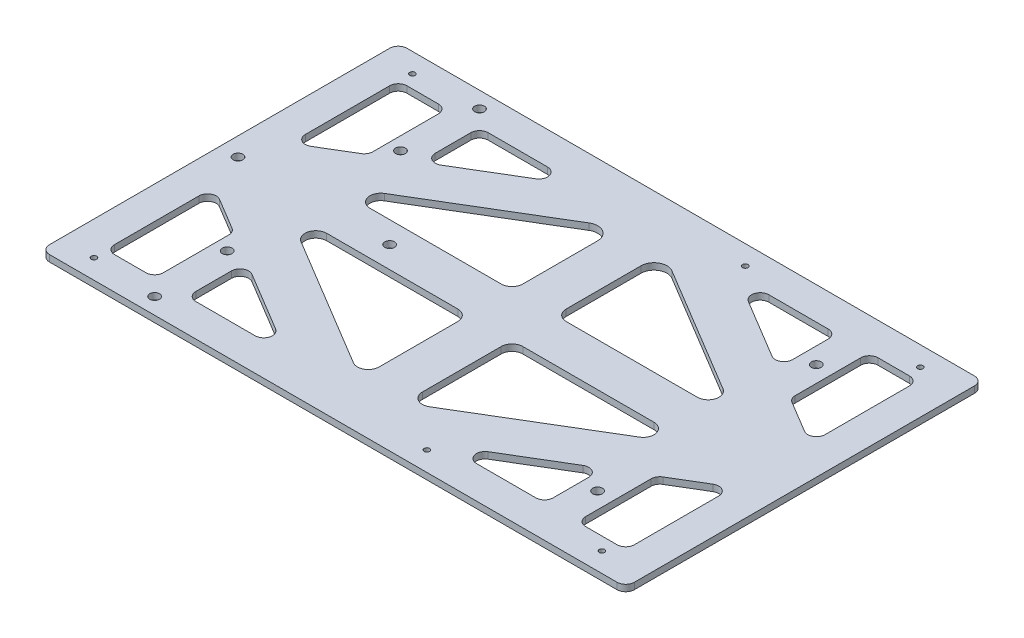
SolidWorks part; units mm, degrees
ref_plane "Alzado" through (0, 0, 0) normal (0, 0, 1) x (1, 0, 0)
ref_plane "Planta" through (0, 0, 0) normal (0, 1, 0) x (1, 0, 0)
ref_plane "Vista lateral" through (0, 0, 0) normal (1, 0, 0) x (0, 0, -1)
sketch "Croquis1" plane through (0, 0, 0) normal (0, 1, 0) x (1, 0, 0)
  line L1 (135, -82.5) -> (-135, -82.5)
  line L2 (135, -82.5) -> (135, 82.5)
  line L3 (135, 82.5) -> (-135, 82.5)
  line L4 (-135, -82.5) -> (-135, 82.5)
  line L5 (135, -82.5) -> (-135, 82.5) construction
  line L6 (135, 82.5) -> (-135, -82.5) construction
  point P0 (0, 0)
  dimension "D1" = 165
  dimension "D2" = 270
extrude "Saliente-Extruir1" add sketch "Croquis1" along normal blind 3
fillet "Redondeo1" radius 4 4 edges at (-135, 1.5, -82.5) (135, 1.5, -82.5) (135, 1.5, 82.5) (-135, 1.5, 82.5)
sketch "Croquis2" plane through (0, 3, 0) normal (0, 1, 0) x (1, 0, 0)
  line L0 (131, 82.5) -> (-131, 82.5) construction
  line L1 (135, -78.5) -> (135, 78.5) construction
  circle A0 centre (90, 50.5) radius 2.25
  dimension "D1" = 4.5
  dimension "D2" = 32
  dimension "D3" = 45
extrude "Cortar-Extruir1" cut sketch "Croquis2" against normal through all
mirror "Simetría1" about plane through (0, 0, 0) normal (0, 0, 1) of "Cortar-Extruir1"
sketch "Croquis3" plane through (0, 3, 0) normal (0, 1, 0) x (1, 0, 0)
  line L0 (-135, 78.5) -> (-135, -78.5) construction
  line L1 (131, 82.5) -> (-131, 82.5) construction
  line L2 (-135, 0) -> (-113.8944, 0) construction
  circle A0 centre (-90, 75) radius 2.25
  circle A1 centre (-90, -75) radius 2.25
  dimension "D1" = 4.5
  dimension "D2" = 45
  dimension "D3" = 7.5
extrude "Cortar-Extruir2" cut sketch "Croquis3" against normal through all
sketch "Croquis4" plane through (0, 3, 0) normal (0, 1, 0) x (1, 0, 0)
  line L0 (0, 82.5) -> (0, -82.5) construction
  line L1 (131, 82.5) -> (-131, 82.5) construction
  line L2 (-131, -82.5) -> (131, -82.5) construction
  line L3 (-135, 0) -> (135, 0) construction
  line L4 (-135, 78.5) -> (-135, -78.5) construction
  line L5 (135, -78.5) -> (135, 78.5) construction
  line L6 (0, -82.5) -> (131, -82.5) construction
  line L7 (135, -82.5) -> (135, 78.5) construction
  line L8 (131, 82.5) -> (0, 82.5) construction
  line L9 (116, 67.5) -> (101.5, 67.5)
  line L12 (110.2817, 0) -> (2.6409, -64.5845) construction
  line L13 (131, 67.5) -> (-131, 67.5) construction
  line L14 (4.9275, 63.2125) -> (110.2817, 0) construction
  line L15 (15, 10) -> (75.5635, 10)
  line L16 (131, 82.5) -> (-131, 82.5) construction
  line L17 (15, -10) -> (75.5635, -10)
  line L18 (10, 49.5719) -> (10, 15)
  line L19 (19.087, 54.7169) -> (78.136, 19.2875)
  line L20 (78.136, -19.2875) -> (17.5725, -55.6256)
  line L24 (49.038, 60.07) -> (76.442, 43.6276)
  line L29 (15.2174, 80.3624) -> (149.1548, 0) construction
  line L30 (90, 50.5) -> (90, 67.5) construction
  line L31 (149.1548, 0) -> (12.9308, -81.7344) construction
  line L32 (99.442, 29.8276) -> (113.942, 21.1276)
  line L34 (82.5, 63.5) -> (82.5, 47.0576)
  line L36 (97.5, 63.5) -> (97.5, 33.2576)
  line L37 (120, 24.5576) -> (120, 63.5)
  line L38 (78.5, 67.5) -> (51.096, 67.5)
  line L39 (10, -15) -> (10, -51.3381)
  arc A0 (78.5, 67.5) -> (82.5, 63.5) centre (78.5, 63.5) cw
  arc A1 (82.5, 47.0576) -> (76.442, 43.6276) centre (78.5, 47.0576) cw
  arc A2 (49.038, 60.07) -> (51.096, 67.5) centre (51.096, 63.5) cw
  arc A3 (120, 63.5) -> (116, 67.5) centre (116, 63.5) ccw
  arc A4 (120, 24.5576) -> (113.942, 21.1276) centre (116, 24.5576) cw
  arc A5 (99.442, 29.8276) -> (97.5, 33.2576) centre (101.5, 33.2576) cw
  arc A6 (101.5, 67.5) -> (97.5, 63.5) centre (101.5, 63.5) ccw
  arc A7 (10, -51.3381) -> (17.5725, -55.6256) centre (15, -51.3381) ccw
  arc A9 (10, 49.5719) -> (19.087, 54.7169) centre (16, 49.5719) cw
  arc A10 (75.5635, 10) -> (78.136, 19.2875) centre (75.5635, 15) ccw
  arc A11 (75.5635, -10) -> (78.136, -19.2875) centre (75.5635, -15) cw
  arc A12 (15, 10) -> (10, 15) centre (15, 15) cw
  arc A13 (15, -10) -> (10, -15) centre (15, -15) ccw
  point P44 (97.5, 30.9929)
  point P64 (10, -10)
  dimension "D5" = 4
  dimension "D6" = 4
  dimension "D7" = 5
  dimension "D13" = 5
  dimension "D14" = 5
  dimension "D2" = 22.43
  dimension "D4" = 15
  dimension "D8" = 15
  dimension "D9" = 38.8724
  dimension "D10" = 10
  dimension "D11" = 10
  dimension "D12" = 10
  dimension "D1" = 15
  dimension "D3" = 20
extrude "Cortar-Extruir3" cut sketch "Croquis4" against normal through all
mirror "Simetría2" about plane through (0, 0, 0) normal (0, 0, 1) of face at (117.4709, 1.5, -21.9597) of face at (106.692, 1.5, -25.4776) of face at (98.2451, 1.5, -31.4147) of face at (97.5, 1.5, -48.3788) of face at (99.0858, 1.5, -65.9142) of face at (108.75, 1.5, -67.5) of face at (118.4142, 1.5, -65.9142) of face at (120, 1.5, -44.0288) of face at (80.9142, 1.5, -65.9142) of face at (82.5, 1.5, -55.2788) of face at (79.9709, 1.5, -44.4597) of face at (62.74, 1.5, -51.8488) of face at (48.6541, 1.5, -64.1764) of face at (64.798, 1.5, -67.5)
mirror "Simetría4" about plane through (0, 0, 0) normal (1, 0, 0) of "Cortar-Extruir3"
mirror "Simetría6" about plane through (0, 0, 0) normal (0, 0, 1) of face at (-64.798, 1.5, -67.5) of face at (-48.6541, 1.5, -64.1764) of face at (-62.74, 1.5, -51.8488) of face at (-79.9709, 1.5, -44.4597) of face at (-80.9142, 1.5, -65.9142) of face at (-82.5, 1.5, -55.2788) of face at (-97.5, 1.5, -48.3788) of face at (-98.2451, 1.5, -31.4147) of face at (-106.692, 1.5, -25.4776) of face at (-117.4709, 1.5, -21.9597) of face at (-120, 1.5, -44.0288) of face at (-99.0858, 1.5, -65.9142) of face at (-118.4142, 1.5, -65.9142) of face at (-108.75, 1.5, -67.5)
sketch "Croquis5" plane through (0, 3, 0) normal (0, 1, 0) x (1, 0, 0)
  line L0 (135, -78.5) -> (135, 78.5) construction
  line L1 (-131, -82.5) -> (131, -82.5) construction
  line L2 (131, 82.5) -> (-131, 82.5) construction
  circle A0 centre (-119.5, 73.5) radius 1.75
  circle A1 centre (34.2, 73.5) radius 1.75
  circle A2 centre (115, 73.5) radius 1.75
  circle A3 centre (115, -73.5) radius 1.75
  circle A4 centre (34.2, -73.5) radius 1.75
  circle A5 centre (-119.5, -73.5) radius 1.75
  point P0 (-119.5, 73.5)
  point P3 (34.2, 73.5)
  point P6 (115, 73.5)
  point P9 (115, -73.5)
  point P12 (34.2, -73.5)
  point P15 (-119.5, -73.5)
  dimension "D1" = 20
  dimension "D2" = 80.8
  dimension "D3" = 153.7
  dimension "D4" = 9
  dimension "D5" = 9
hole_wizard "Taladro roscado M31" positions "Croquis5" profile "Croquis6" tap size "M3" standard "ISO"
sketch "Croquis6" plane through (-119.5, 3, -73.5) normal (1, 0, 0) x (0, 0, 1)
  line L0 (0, 0) -> (0, 9.2511)
  line L1 (0, 9.2511) -> (1.25, 8.5)
  line L2 (1.25, 8.5) -> (1.25, 0)
  line L5 (1.25, 0) -> (0, 0)
  line L10 (0, 9.2511) -> (-1.25, 8.5) construction
  line L11 (0, -6.35) -> (0, 107.95) construction
  dimension "Diámetro de perforador para roscar" = 2.5
  dimension "Profundidad de perforador para roscar" = 8.5
  dimension "Ángulo de perforador" = 118
cosmetic thread "Rosca de taladro1" parameters "D1"=6, "D2"=3
cosmetic thread "Rosca de taladro2" parameters "D1"=6, "D2"=3
cosmetic thread "Rosca de taladro3" parameters "D1"=6, "D2"=3
cosmetic thread "Rosca de taladro4" parameters "D1"=6, "D2"=3
cosmetic thread "Rosca de taladro5" parameters "D1"=6, "D2"=3
cosmetic thread "Rosca de taladro6" parameters "D1"=6, "D2"=3
sketch "Croquis9" plane through (0, 3, 0) normal (0, 1, 0) x (1, 0, 0)
  circle A0 centre (-126.5, 0) radius 2.25
  circle A1 centre (-91.5, 40) radius 2.25
  circle A2 centre (-56.5, 0) radius 2.25
  circle A3 centre (-91.5, -40) radius 2.25
  point P0 (-126.5, 0)
  point P1 (-91.5, -40)
  point P3 (-56.5, 0)
  point P5 (-91.5, 40)
  dimension "D1" = 4.5
extrude "Cortar-Extruir4" cut sketch "Croquis9" against normal blind 4
